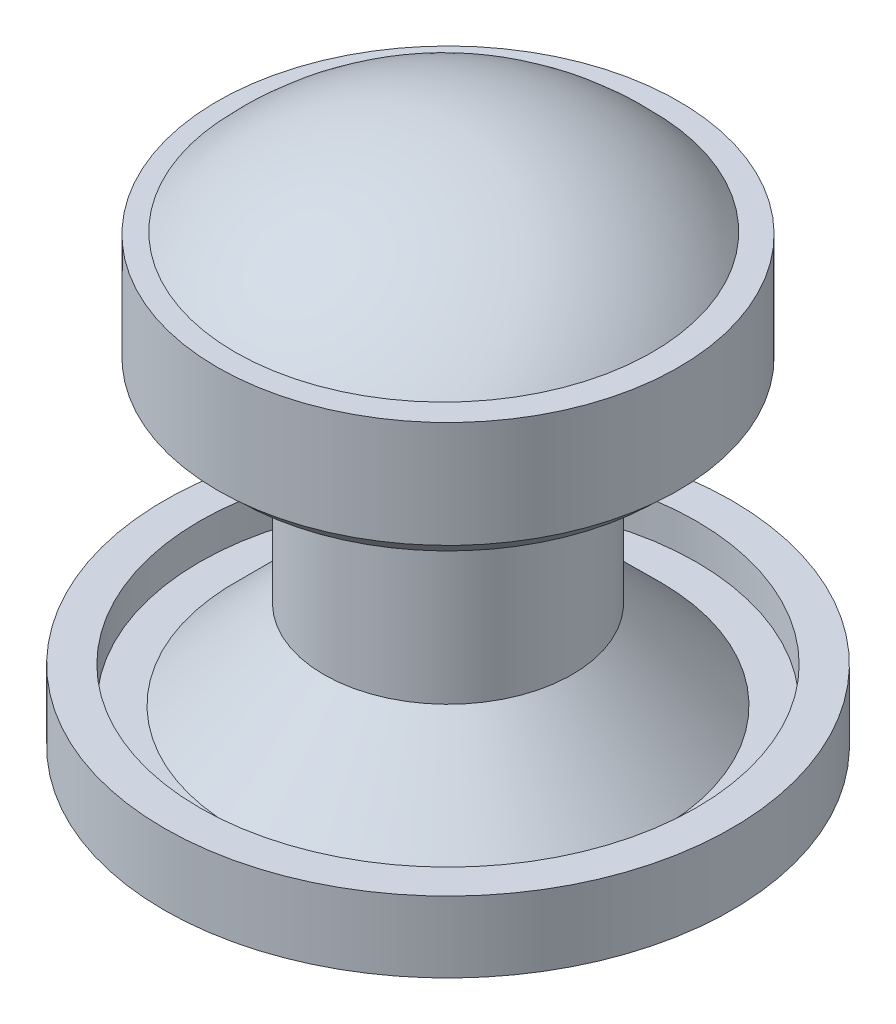
SolidWorks part; units mm, degrees
ref_plane "Front" through (0, 0, 0) normal (0, 0, 1) x (1, 0, 0)
ref_plane "Top" through (0, 0, 0) normal (0, 1, 0) x (1, 0, 0)
ref_plane "Right" through (0, 0, 0) normal (1, 0, 0) x (0, 0, -1)
sketch "Sketch1" plane through (0, 0, 0) normal (0, 1, 0) x (1, 0, 0)
  circle A0 centre (0, 0) radius 8
  dimension "D1" = 16
extrude "Boss-Extrude1" add sketch "Sketch1" along normal blind 1
sketch "Sketch2" plane through (0, 1, 0) normal (0, 1, 0) x (1, 0, 0)
  circle A0 centre (0, 0) radius 6
  dimension "D1" = 12
extrude "Boss-Extrude2" add sketch "Sketch2" along normal blind 2.5 draft 45 contours A0
sketch "Sketch3" plane through (0, 3.5, 0) normal (0, 1, 0) x (1, 0, 0)
  circle A1 centre (0, 0) radius 3.5
  circle A2 centre (0, 0) radius 3.5
  dimension "D1" = 0
extrude "Boss-Extrude3" add sketch "Sketch3" along normal blind 4
sketch "Sketch4" plane through (0, 7.5, 0) normal (0, 1, 0) x (1, 0, 0)
  circle A1 centre (0, 0) radius 3.5
  circle A2 centre (0, 0) radius 3.5
  dimension "D1" = 0
extrude "Boss-Extrude4" add sketch "Sketch4" along normal blind 1 draft 59 draft outward yes
sketch "Sketch6" plane through (0, 8.5, 0) normal (0, 1, 0) x (1, 0, 0)
  circle A1 centre (0, 0) radius 5.1643
  circle A2 centre (0, 0) radius 5.1643
  dimension "D1" = 0
extrude "Boss-Extrude5" add sketch "Sketch6" along normal blind 1
sketch "Sketch7" plane through (0, 9.5, 0) normal (0, 1, 0) x (1, 0, 0)
  circle A0 centre (0, 0) radius 6.5
  dimension "D1" = 13
extrude "Boss-Extrude6" add sketch "Sketch7" along normal blind 3
sketch "Sketch8" plane through (0, 0, 0) normal (0, 0, 1) x (1, 0, 0)
  line L0 (-6, 12.5) -> (5.76, 12.5)
  line L1 (-0.12, 12.5) -> (-0.12, 15.0755)
  line L2 (6.5, 12.5) -> (-6.5, 12.5) construction
  arc A0 (-6, 12.5) -> (5.76, 12.5) centre (-0.12, 7.0755) cw
  dimension "D1" = 8
  dimension "D2" = 0.5
  dimension "D3" = 0.74
revolve "Revolve1" add sketch "Sketch8" angle 360 about L1 region at (-2.3815, 13.5459, 0)
sketch "Sketch9" plane through (0, 1, 0) normal (0, 1, 0) x (1, 0, 0)
  circle A0 centre (0, 0) radius 7
  circle A1 centre (0, 0) radius 8
  circle A5 centre (0, 0) radius 8
  dimension "D1" = 0
extrude "Boss-Extrude7" add sketch "Sketch9" along normal blind 1
sketch "Sketch10" plane through (0, 0, 0) normal (0, -1, 0) x (1, 0, 0)
  circle A0 centre (0, 0) radius 1.4
  dimension "D1" = 2.8
extrude "Cut-Extrude1" cut sketch "Sketch10" against normal blind 6
chamfer "Chamfer1" distance 1.3 angle 45 1 edges at (0, 9.5, 5.1643)
